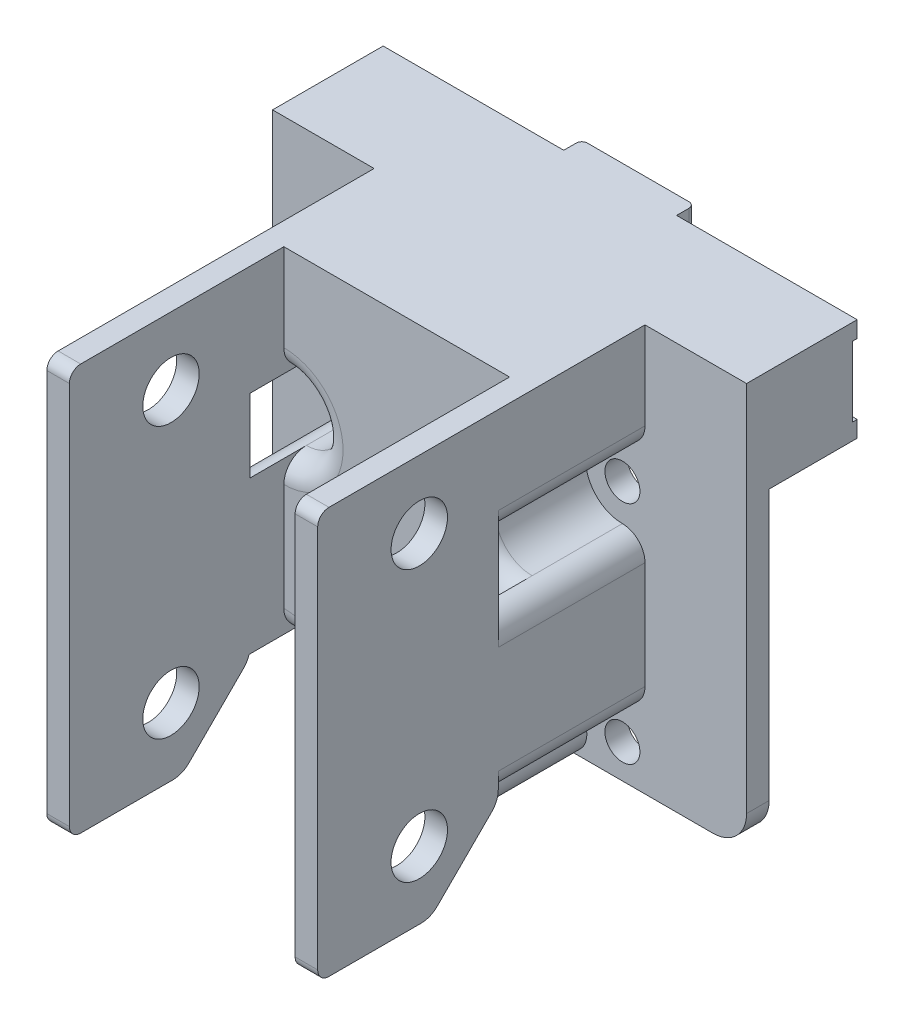
SolidWorks part; units mm, degrees
material "6063-T5"
ref_plane "Front Plane" through (0, 0, 0) normal (1, 0, 0) x (0, 1, 0)
ref_plane "Top Plane" through (0, 0, 0) normal (0, 0, 1) x (0, 1, 0)
ref_plane "Right Plane" through (0, 0, 0) normal (0, 1, 0) x (-1, 0, 0)
sketch "Sketch1" plane through (0, 0, 0) normal (0, 0, 1) x (0, 1, 0)
  line L0 (-13, 0) -> (0, 0) construction
  line L5 (-13, 21) -> (23, 21)
  line L6 (-13, 21) -> (-13, -21)
  line L7 (-10, -10) -> (10, -10) construction
  line L8 (-10, -10) -> (-10, 10) construction
  line L9 (-10, 10) -> (10, 10) construction
  line L10 (10, -10) -> (10, 10) construction
  line L11 (-10, -10) -> (10, 10) construction
  line L12 (-10, 10) -> (10, -10) construction
  line L13 (-13, -21) -> (23, -21)
  line L14 (23, 21) -> (23, -21)
  circle A0 centre (-10, -10) radius 1.55
  circle A1 centre (10, -10) radius 1.55
  circle A2 centre (10, 10) radius 1.55
  circle A3 centre (-10, 10) radius 1.55
  point P0 (0, 0)
  point P5 (0, 0)
  dimension "D2" = 3.1
  dimension "D1" = 20
  dimension "D3" = 42
  dimension "D4" = 13
  dimension "D5" = 23
extrude "Boss-Extrude1" add sketch "Sketch1" along normal blind 2
sketch "Sketch5" plane through (0, 0, 0) normal (0, 0, 1) x (1, 0, 0)
  line L0 (21, -13) -> (21, 23) construction
  line L1 (-21, 23) -> (21, 23)
  line L2 (-21, 23) -> (-21, 13.9)
  line L3 (-21, 13.9) -> (21, 13.9)
  line L4 (21, 23) -> (21, 13.9)
  dimension "D1" = 9.1
extrude "Boss-Extrude2" add sketch "Sketch5" against normal blind 7.4
sketch "Sketch6" plane through (0, 0, -7.4) normal (0, 0, -1) x (1, 0, 0)
  line L0 (-21, -13.9) -> (21, -13.9) construction
  line L3 (-5, -13.9) -> (5, -13.9)
  line L4 (-5, -13.9) -> (-5, -23)
  line L5 (-5, -23) -> (5, -23)
  line L6 (5, -13.9) -> (5, -23)
  line L7 (21, -23) -> (-21, -23) construction
  line L8 (0, -13.9) -> (0, 0) construction
  dimension "D1" = 10
extrude "Boss-Extrude3" add sketch "Sketch6" along normal blind 2
sketch "Sketch2" plane through (0, 0, -9.4) normal (0, 0, -1) x (1, 0, 0)
  line L0 (-21, -18.5) -> (21, -18.5) construction
  line L1 (-21, -13.9) -> (-21, 13) construction
  line L2 (21, 13) -> (21, -13.9) construction
  line L3 (21, -23) -> (-21, -23) construction
  line L5 (-20, -23) -> (20, -23)
  line L6 (-20, -23) -> (-20, -14)
  line L7 (-20, -14) -> (20, -14)
  line L8 (20, -23) -> (20, -14)
  line L9 (-20, -23) -> (20, -14) construction
  line L10 (-20, -14) -> (20, -23) construction
  circle A0 centre (0, -18.5) radius 3
  dimension "D1" = 4.5
  dimension "D2" = 6
  dimension "D3" = 9
  dimension "D4" = 40
extrude "Cut-Extrude1" cut sketch "Sketch2" against normal blind 6 contours A0 region at (0, 18.5, -9.4)
sketch "Sketch4" plane through (0, 0, -7.4) normal (0, 0, -1) x (1, 0, 0)
  line L0 (-5, -13.9) -> (-5, -23) construction
  line L15 (-21, -13.9) -> (-5, -13.9)
  line L16 (-21, -13.9) -> (-21, -15.35)
  line L17 (-21, -15.35) -> (-5, -15.35)
  line L18 (-5, -13.9) -> (-5, -15.35)
  line L19 (-21, -23) -> (-21, -13.9) construction
  line L20 (-5, -23) -> (-21, -23)
  line L21 (-5, -23) -> (-5, -21.55)
  line L22 (-5, -21.55) -> (-21, -21.55)
  line L23 (-21, -23) -> (-21, -21.55)
  line L24 (5, -23) -> (5, -13.9) construction
  line L25 (21, -13.9) -> (5, -13.9)
  line L26 (21, -13.9) -> (21, -15.35)
  line L27 (21, -15.35) -> (5, -15.35)
  line L28 (5, -13.9) -> (5, -15.35)
  line L29 (21, -13.9) -> (21, -23) construction
  line L30 (5, -23) -> (21, -23)
  line L31 (5, -23) -> (5, -21.55)
  line L32 (5, -21.55) -> (21, -21.55)
  line L33 (21, -23) -> (21, -21.55)
  dimension "D1" = 6.2
extrude "Boss-Extrude4" add sketch "Sketch4" along normal blind 0.4
fillet "Fillet2" radius 3 2 edges at (-21, -13, 1) (21, -13, 1)
fillet "Fillet3" radius 0.5 2 edges at (5, 18.45, -9.4) (-5, 18.45, -9.4)
sketch "Sketch8" plane through (0, 0, 2) normal (0, 0, 1) x (1, 0, 0)
  line L0 (0, 0) -> (0, -13) construction
  line L1 (12, -13) -> (-12, -13)
  line L2 (12, -13) -> (12, 23)
  line L3 (12, 23) -> (-12, 23)
  line L4 (-12, -13) -> (-12, 23)
  line L5 (21, 23) -> (-21, 23) construction
  line L6 (-18, -13) -> (18, -13) construction
  circle A0 centre (-10, -10) radius 3.25 construction
  circle A1 centre (-10, 10) radius 3.25 construction
  circle A2 centre (10, 10) radius 3.25 construction
  circle A3 centre (10, -10) radius 3.25 construction
  point P0 (0, 0)
  point P26 (12, 6.1758)
  dimension "D2" = 6.5
  dimension "D1" = 24
  dimension "D4" = 13
extrude "Boss-Extrude5" add sketch "Sketch8" along normal blind 10
sketch "Sketch9" plane through (0, 0, 12) normal (0, 0, 1) x (1, 0, 0)
  line L0 (-12, -13) -> (12, -13) construction
  line L1 (-12, 23) -> (-10, 23)
  line L2 (-12, 23) -> (-12, -13)
  line L3 (-12, -13) -> (-10, -13)
  line L4 (-10, 23) -> (-10, -13)
  line L5 (-12, -13) -> (-18, -13) construction
  line L6 (12, 23) -> (10, 23)
  line L7 (12, 23) -> (12, -13)
  line L8 (12, -13) -> (10, -13)
  line L9 (10, 23) -> (10, -13)
  dimension "D1" = 2
extrude "Boss-Extrude6" add sketch "Sketch9" along normal blind 19
sketch "Sketch10" plane through (12, 0, 0) normal (1, 0, 0) x (0, 1, 0)
  line L0 (-13, 12) -> (23, 12) construction
  line L3 (23, 31) -> (23, 2) construction
  line L5 (-13, 12) -> (23, 12) construction
  line L6 (5, 12) -> (5, 31) construction
  line L7 (-13, 31) -> (23, 31) construction
  circle A0 centre (17, 22) radius 2.5
  circle A1 centre (17, 22) radius 4.5 construction
  circle A2 centre (-7, 22) radius 4.5 construction
  circle A3 centre (-7, 22) radius 2.5
  dimension "D1" = 5
  dimension "D2" = 9
  dimension "D4" = 10
  dimension "D3" = 6
extrude "Cut-Extrude2" cut sketch "Sketch10" against normal up to surface (24 mm away) up to face at (-12, 5, 16.5)
fillet "Fillet4" radius 1 4 edges at (11, -13, 31) (11, 23, 31) (-11, 23, 31) (-11, -13, 31)
sketch "Sketch11" plane through (0, 0, 2) normal (0, 0, 1) x (1, 0, 0)
  line L0 (-13.25, -10) -> (-13.25, -13)
  line L2 (-13.25, -13) -> (-11.25, -13)
  line L3 (-10, -13) -> (-12, -13) construction
  line L4 (13.25, -10) -> (13.25, -13)
  line L6 (13.25, -13) -> (11.25, -13)
  line L8 (12, -13) -> (10, -13) construction
  line L9 (12, -13) -> (18, -13) construction
  circle A27 centre (-10, 10) radius 3.25
  circle A28 centre (10, 10) radius 3.25
  arc A29 (13.25, -10) -> (11.25, -13) centre (10, -10) ccw
  arc A30 (-11.25, -13) -> (-13.25, -10) centre (-10, -10) ccw
  circle A31 centre (-10, -10) radius 3.25 construction
  circle A32 centre (10, -10) radius 3.25 construction
  circle A33 centre (10, 10) radius 3.25 construction
  circle A34 centre (-10, 10) radius 3.25 construction
  point P3 (0, 0)
  point P5 (13.25, -13)
  point P16 (-13.25, -13)
  point P25 (11.25, -13)
  point P29 (0, 0)
extrude "Cut-Extrude3" cut sketch "Sketch11" along normal blind 13
chamfer "Chamfer1" distance 6 angle 45 2 edges at (-11, -13, 15) (11, -13, 15)
sketch "Sketch12" plane through (-12, 0, 0) normal (-1, 0, 0) x (0, -1, 0)
  circle A0 centre (-17, 22) radius 4.75 construction
  circle A1 centre (7, 22) radius 4.75 construction
  dimension "D1" = 9.5
fillet "Fillet6" radius 2 8 edges at (-12, 7.4383, 8.5) (-12, 12.5617, 8.5) (12, 12.5617, 8.5) (12, 7.4383, 8.5) (12, -7.4383, 8.7191) (-12, -7.4383, 8.7191) (8.75, -13, 7) (-8.75, -13, 7)
fillet "Fillet7" radius 2 11 edges at (7.4926, -7.9323, 12) (6.3892, -12.2724, 12) (0, -13, 12) (-6.3892, -12.2724, 12) (-7.4926, -7.9323, 12) (6.75, 10, 12) (-6.75, 10, 12) (-11, -13, 21) (-11, -7, 15) (11, -13, 21) (11, -7, 15)
